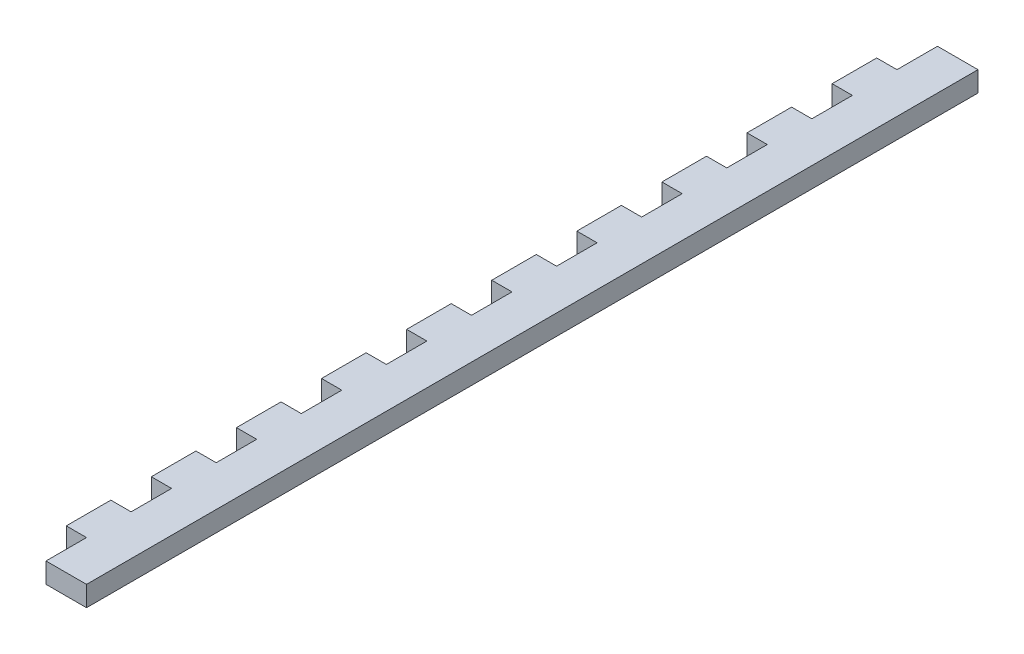
SolidWorks part; units mm, degrees
material "Acrylic (Medium-high impact)"
ref_plane "Front" through (0, 0, 0) normal (0, 0, 1) x (1, 0, 0)
ref_plane "Top" through (0, 0, 0) normal (0, 1, 0) x (1, 0, 0)
ref_plane "Right" through (0, 0, 0) normal (1, 0, 0) x (0, 0, -1)
sketch "Sketch1" plane through (0, 0, 0) normal (1, 0, 0) x (0, 0, -1)
  line L1 (-139.7, 142.875) -> (139.7, 142.875)
  line L2 (-139.7, 142.875) -> (-139.7, -142.875)
  line L3 (-139.7, -142.875) -> (139.7, -142.875)
  line L4 (139.7, 142.875) -> (139.7, -142.875)
  point P4 (-139.7, 0)
  point P6 (0, 142.875)
  dimension "D1" = 285.75
  dimension "D2" = 279.4
extrude "Boss-Extrude1" add sketch "Sketch1" along normal blind 6.35
sketch "Sketch2" plane through (6.35, 0, 0) normal (1, 0, 0) x (0, 0, -1)
  line L0 (139.7, -142.875) -> (139.7, 142.875) construction
  line L1 (-139.7, 142.875) -> (139.7, 142.875)
  line L2 (-139.7, 142.875) -> (-139.7, 136.525)
  line L3 (-139.7, 136.525) -> (139.7, 136.525)
  line L4 (139.7, 142.875) -> (139.7, 136.525)
  dimension "D1" = 6.35
extrude "Boss-Extrude2" add sketch "Sketch2" along normal blind 12.7
sketch "Sketch3" plane through (0, 0, 0) normal (-1, 0, 0) x (0, 0, 1)
  line L0 (-114.3, -85.725) -> (-25.4, -85.725)
  line L1 (-25.4, -111.125) -> (-114.3, -111.125)
  line L2 (12.7, 142.875) -> (12.7, -142.875) construction
  line L3 (-139.7, 142.875) -> (139.7, 142.875) construction
  line L4 (139.7, -142.875) -> (-139.7, -142.875) construction
  line L5 (139.7, 142.875) -> (139.7, -142.875) construction
  arc A0 (-25.4, -85.725) -> (-25.4, -111.125) centre (-25.4, -98.425) cw
  arc A1 (-114.3, -111.125) -> (-114.3, -85.725) centre (-114.3, -98.425) cw
  dimension "D1" = 25.4
  dimension "D3" = 88.9
  dimension "D2" = 38.1
  dimension "D4" = 127
  dimension "D5" = 44.45
extrude "Cut-Extrude1" cut sketch "Sketch3" against normal through all
sketch "Sketch4" plane through (0, 0, 0) normal (-1, 0, 0) x (0, 0, 1)
  line L0 (-113.03, 142.875) -> (-100.33, 142.875)
  line L1 (-139.7, 142.875) -> (-127, 142.875)
  line L2 (-139.7, 142.875) -> (-139.7, 136.525)
  line L3 (-139.7, 136.525) -> (-127, 136.525)
  line L4 (-127, 142.875) -> (-127, 136.525)
  line L5 (-113.03, 142.875) -> (-113.03, 136.525)
  line L6 (-113.03, 136.525) -> (-100.33, 136.525)
  line L7 (-100.33, 142.875) -> (-100.33, 136.525)
  line L8 (-86.36, 142.875) -> (-73.66, 142.875)
  line L9 (-86.36, 142.875) -> (-86.36, 136.525)
  line L10 (-86.36, 136.525) -> (-73.66, 136.525)
  line L11 (-73.66, 142.875) -> (-73.66, 136.525)
  line L12 (-59.69, 142.875) -> (-46.99, 142.875)
  line L13 (-59.69, 142.875) -> (-59.69, 136.525)
  line L14 (-59.69, 136.525) -> (-46.99, 136.525)
  line L15 (-46.99, 142.875) -> (-46.99, 136.525)
  line L16 (-33.02, 142.875) -> (-20.32, 142.875)
  line L17 (-33.02, 142.875) -> (-33.02, 136.525)
  line L18 (-33.02, 136.525) -> (-20.32, 136.525)
  line L19 (-20.32, 142.875) -> (-20.32, 136.525)
  line L20 (-6.35, 142.875) -> (6.35, 142.875)
  line L21 (-6.35, 142.875) -> (-6.35, 136.525)
  line L22 (-6.35, 136.525) -> (6.35, 136.525)
  line L23 (6.35, 142.875) -> (6.35, 136.525)
  line L24 (20.32, 142.875) -> (33.02, 142.875)
  line L25 (20.32, 142.875) -> (20.32, 136.525)
  line L26 (20.32, 136.525) -> (33.02, 136.525)
  line L27 (33.02, 142.875) -> (33.02, 136.525)
  line L28 (46.99, 142.875) -> (59.69, 142.875)
  line L29 (46.99, 142.875) -> (46.99, 136.525)
  line L30 (46.99, 136.525) -> (59.69, 136.525)
  line L31 (59.69, 142.875) -> (59.69, 136.525)
  line L32 (73.66, 142.875) -> (86.36, 142.875)
  line L33 (73.66, 142.875) -> (73.66, 136.525)
  line L34 (73.66, 136.525) -> (86.36, 136.525)
  line L35 (86.36, 142.875) -> (86.36, 136.525)
  line L36 (100.33, 142.875) -> (113.03, 142.875)
  line L37 (100.33, 142.875) -> (100.33, 136.525)
  line L38 (100.33, 136.525) -> (113.03, 136.525)
  line L39 (113.03, 142.875) -> (113.03, 136.525)
  line L40 (127, 142.875) -> (139.7, 142.875)
  line L41 (127, 142.875) -> (127, 136.525)
  line L42 (127, 136.525) -> (139.7, 136.525)
  line L43 (139.7, 142.875) -> (139.7, 136.525)
  line L69 (-139.7, 142.875) -> (139.7, 142.875)
  line L70 (-139.7, 142.875) -> (-139.7, 136.525)
  line L71 (-139.7, 136.525) -> (139.7, 136.525)
  line L72 (139.7, 142.875) -> (139.7, 136.525)
  line M73 (139.7, -142.875) -> (139.7, 142.875)
  line M74 (139.7, 142.875) -> (-139.7, 142.875)
  line M75 (-139.7, 142.875) -> (-139.7, -142.875)
  dimension "D1" = 6.35
  dimension "D2" = 12.7
  dimension "D3" = 11
sketch "Sketch5" plane through (0, 0, -139.7) normal (0, 0, -1) x (-1, 0, 0)
  line L1 (45.8749, 136.525) -> (-19.05, 136.525)
  line L2 (45.8749, 136.525) -> (45.8749, -231.4418)
  line L3 (45.8749, -231.4418) -> (-19.05, -231.4418)
  line L4 (-19.05, 136.525) -> (-19.05, -231.4418)
  point P5 (-6.35, 100.9476)
  point P6 (9.8625, 85.0909)
  point P7 (-19.05, 136.525)
  point P8 (0, 0)
  point P9 (-6.35, 87.32)
  point P11 (45.8749, -231.4418)
extrude "Cut-Extrude2" cut sketch "Sketch5" against normal through all
extrude "Cut-Extrude3" cut sketch "Sketch4" against normal blind 6.35 contours L7 L5 L6 M74 | L11 L9 L10 M74 | L15 L13 L14 M74 | L19 L17 L18 M74 | L23 L21 L22 M74 | L27 L25 L26 M74 | L31 L29 L30 M74 | L35 L33 L34 M74 | L39 L37 L38 M74 | L41 L42 M73 M74 | L4 L3 M74 M75 region at (0, 139.7, -106.68) region at (0, 139.7, -133.35) region at (0, 139.7, -80.01) region at (0, 139.7, -53.34) region at (0, 139.7, -26.67) region at (0, 139.7, 0) region at (0, 139.7, 26.67) region at (0, 139.7, 53.34) region at (0, 139.7, 80.01) region at (0, 139.7, 106.68) region at (0, 139.7, 133.35)
